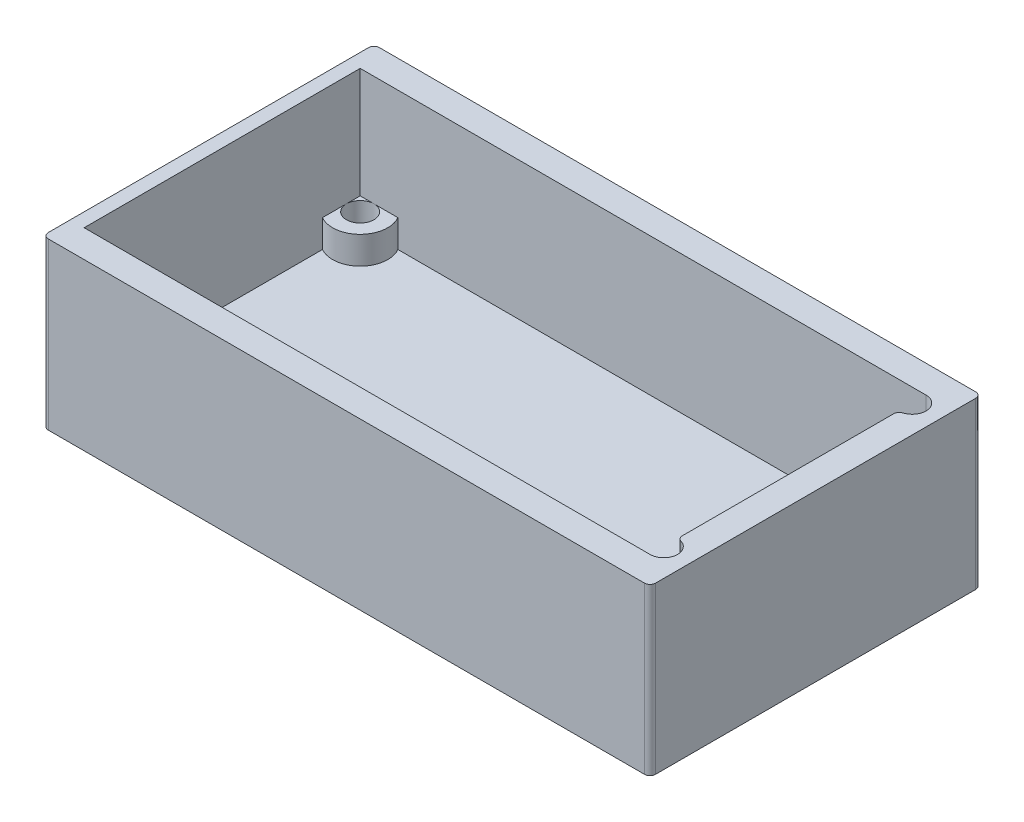
SolidWorks part; units mm, degrees
ref_plane "Front Plane" through (0, 0, 0) normal (0, 0, 1) x (1, 0, 0)
ref_plane "Top Plane" through (0, 0, 0) normal (0, 1, 0) x (1, 0, 0)
ref_plane "Right Plane" through (0, 0, 0) normal (1, 0, 0) x (0, 0, -1)
sketch "Sketch1" plane through (0, 0, 0) normal (0, 1, 0) x (1, 0, 0)
  line L1 (-11, -6) -> (11, -6)
  line L2 (-11, -6) -> (-11, 6)
  line L3 (-11, 6) -> (11, 6)
  line L4 (11, -6) -> (11, 6)
  line L5 (-11, -6) -> (11, 6) construction
  line L6 (-11, 6) -> (11, -6) construction
  point P0 (0, 0)
  dimension "D1" = 12
  dimension "D2" = 22
extrude "Boss-Extrude1" add sketch "Sketch1" along normal blind 6
fillet "Fillet1" radius 0.2 4 edges at (-11, 3, -6) (11, 3, -6) (11, 3, 6) (-11, 3, 6)
sketch "Sketch2" plane through (0, 6, 0) normal (0, 1, 0) x (1, 0, 0)
  line L0 (11, -5.8) -> (11, 5.8) construction
  line L1 (-10.5, -5) -> (10, -5)
  line L2 (-10.5, -5) -> (-10.5, 5)
  line L3 (-10.5, 5) -> (10, 5)
  line L4 (10, -5) -> (10, 5)
  line L5 (-10.5, -5) -> (10, 5) construction
  line L6 (-10.5, 5) -> (10, -5) construction
  line L7 (10.8, 6) -> (-10.8, 6) construction
  line L8 (-10.8, -6) -> (10.8, -6) construction
  line L9 (-11, 5.8) -> (-11, -5.8) construction
  point P0 (-0.25, 0)
  dimension "D1" = 10
  dimension "D2" = 20.5
  dimension "D3" = 1
  dimension "D4" = 1
  dimension "D5" = 1
  dimension "D6" = 0.5
extrude "Cut-Extrude1" cut sketch "Sketch2" against normal blind 5
sketch "Sketch3" plane through (0, 1, 0) normal (0, 1, 0) x (1, 0, 0)
  circle A0 centre (10, 4.5) radius 1
  circle A1 centre (10, 4.5) radius 0.5
extrude "Boss-Extrude2" add sketch "Sketch3" along normal blind 1
mirror "Mirror1" about plane through (0, 0, 0) normal (0, 0, 1) of "Boss-Extrude2"
sketch "Sketch7" plane through (0, 1, 0) normal (0, 1, 0) x (1, 0, 0)
  circle A0 centre (-10, 4.5) radius 1
  circle A1 centre (-10, 4.5) radius 0.5
extrude "Boss-Extrude3" add sketch "Sketch7" along normal blind 1
mirror "Mirror3" about plane through (0, 0, 0) normal (0, 0, 1) of "Boss-Extrude3"
sketch "Sketch8" plane through (0, 6, 0) normal (0, 1, 0) x (1, 0, 0)
  line L0 (10, 4) -> (10, 5) construction
  circle A0 centre (10, 4.5) radius 0.5
extrude "Cut-Extrude4" cut sketch "Sketch8" against normal through all
mirror "Mirror4" about plane through (0, 0, 0) normal (0, 0, 1) of "Cut-Extrude4"
fillet "Fillet2" radius 0.2 2 edges at (10, 4, 4) (10, 4, -4)
mirror "Mirror5" about plane through (0, 0, 0) normal (1, 0, 0) of "Mirror4"
sketch "Sketch9" plane through (0, 0, 0) normal (0, -1, 0) x (-1, 0, 0)
  circle A0 centre (-10, -4.5) radius 0.9
extrude "Cut-Extrude12" cut sketch "Sketch9" against normal blind 1
mirror "Mirror6" about plane through (0, 0, 0) normal (1, 0, 0) of "Cut-Extrude12"
mirror "Mirror7" about plane through (0, 0, 0) normal (0, 0, 1) of "Mirror6"
